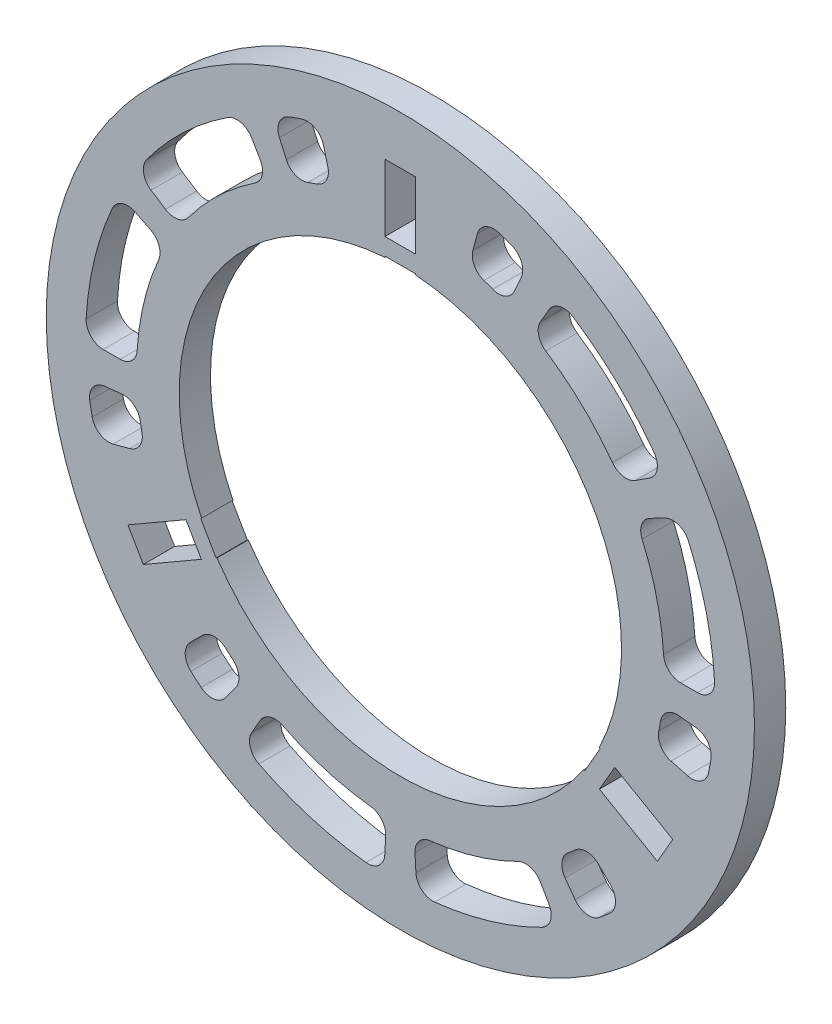
SolidWorks part; units mm, degrees
ref_plane "Front Plane" through (0, 0, 0) normal (0, 0, 1) x (1, 0, 0)
ref_plane "Top Plane" through (0, 0, 0) normal (0, 1, 0) x (1, 0, 0)
ref_plane "Right Plane" through (0, 0, 0) normal (1, 0, 0) x (0, 0, -1)
sketch "Sketch1" plane through (0, 0, 0) normal (0, 0, 1) x (1, 0, 0)
  line L0 (0, 0) -> (0, 50.8) construction
  line L1 (47.9712, -31.0114) -> (50.8422, -26.0386)
  line L2 (2.871, 57.05) -> (-2.871, 57.05)
  line L3 (2.871, 57.05) -> (2.871, 44.55)
  line L4 (2.871, 44.55) -> (-2.871, 44.55)
  line L5 (-2.871, 57.05) -> (-2.871, 44.55)
  line L6 (2.871, 57.05) -> (-2.871, 44.55) construction
  line L7 (2.871, 44.55) -> (-2.871, 57.05) construction
  line L8 (47.9712, -31.0114) -> (37.1459, -24.7614)
  line L9 (37.1459, -24.7614) -> (40.0169, -19.7886)
  line L10 (50.8422, -26.0386) -> (40.0169, -19.7886)
  line L11 (47.9712, -31.0114) -> (40.0169, -19.7886) construction
  line L12 (37.1459, -24.7614) -> (50.8422, -26.0386) construction
  line L13 (-50.8422, -26.0386) -> (-47.9712, -31.0114)
  line L14 (-50.8422, -26.0386) -> (-40.0169, -19.7886)
  line L15 (-40.0169, -19.7886) -> (-37.1459, -24.7614)
  line L16 (-47.9712, -31.0114) -> (-37.1459, -24.7614)
  line L17 (-50.8422, -26.0386) -> (-37.1459, -24.7614) construction
  line L18 (-40.0169, -19.7886) -> (-47.9712, -31.0114) construction
  line L19 (-2.871, 41.375) -> (2.871, 41.375)
  line L20 (-2.871, 41.175) -> (-2.871, 41.375)
  line L21 (2.871, 41.175) -> (2.871, 41.375)
  line L22 (34.2231, -23.0739) -> (34.3963, -23.1739)
  line L23 (37.2673, -18.2011) -> (34.3963, -23.1739)
  line L24 (37.0941, -18.1012) -> (37.2673, -18.2011)
  line L25 (-37.0941, -18.1012) -> (-37.2673, -18.2011)
  line L26 (-34.3963, -23.1739) -> (-37.2673, -18.2011)
  line L27 (0, 0) -> (32.5438, 56.3674) construction
  line L28 (-34.2231, -23.0739) -> (-34.3963, -23.1739)
  arc A0 (-2.871, 41.175) -> (-37.0941, -18.1012) centre (0, 0) ccw
  circle A1 centre (0, 0) radius 65.0875
  circle A2 centre (0, 0) radius 50.8 construction
  arc A3 (37.0941, -18.1012) -> (2.871, 41.175) centre (0, 0) ccw
  arc A4 (-34.2231, -23.0739) -> (34.2231, -23.0739) centre (0, 0) ccw
  point P21 (0, 0)
  point P32 (0, 0)
  point P34 (0, 0)
  dimension "D1" = 82.55
  dimension "D2" = 130.175
  dimension "D8" = 3.175
  dimension "D10" = 101.6
  dimension "D3" = 50.8
  dimension "D4" = 12.5
  dimension "D5" = 5.742
  dimension "D7" = 30
  dimension "D6" = 3
  dimension "D9" = 3
extrude "Boss-Extrude1" add sketch "Sketch1" along normal blind 5.842
sketch "Sketch3" plane through (0, 0, 5.842) normal (0, 0, 1) x (1, 0, 0)
  line L0 (0, 0) -> (0, 65.0875) construction
  line L1 (0, 0) -> (-56.3674, 32.5437) construction
  line L2 (-24.6063, 42.6193) -> (-29.3688, 50.8682)
  line L3 (-49.2125, 0) -> (-58.7375, 0)
  line L4 (-41.2731, 26.803) -> (-49.2614, 31.9907)
  line L5 (-43.8487, 22.342) -> (-52.3355, 26.6663)
  line L6 (43.8487, 22.342) -> (52.3355, 26.6663)
  line L7 (41.2731, 26.803) -> (49.2614, 31.9907)
  line L8 (24.6063, 42.6193) -> (29.3688, 50.8682)
  line L9 (49.2125, 0) -> (58.7375, 0)
  line L10 (-2.5756, -49.1451) -> (-3.0741, -58.657)
  line L11 (2.5756, -49.1451) -> (3.0741, -58.657)
  line L12 (24.6062, -42.6193) -> (29.3687, -50.8682)
  line L13 (-24.6063, -42.6193) -> (-29.3688, -50.8682)
  line L14 (-20.0165, 44.9579) -> (-23.8907, 53.6594)
  line L15 (-15.2024, 56.7361) -> (-12.7371, 47.5356)
  line L16 (-56.7361, -15.2024) -> (-47.5356, -12.7371)
  line L17 (-48.9429, -5.1441) -> (-58.4157, -6.1397)
  line L18 (48.9429, -5.1441) -> (58.4157, -6.1397)
  line L19 (56.7361, -15.2024) -> (47.5356, -12.7371)
  line L20 (15.2024, 56.7361) -> (12.7371, 47.5356)
  line L21 (20.0165, 44.9579) -> (23.8907, 53.6594)
  line L22 (-28.9264, -39.8137) -> (-34.525, -47.5196)
  line L23 (-41.5337, -41.5337) -> (-34.7985, -34.7985)
  line L24 (41.5337, -41.5337) -> (34.7985, -34.7985)
  line L25 (28.9264, -39.8137) -> (34.525, -47.5196)
  circle A0 centre (0, 0) radius 65.0875 construction
  arc A1 (-29.3688, 50.8682) -> (-49.2614, 31.9907) centre (0, 0) ccw
  arc A2 (-24.6063, 42.6193) -> (-41.2731, 26.803) centre (0, 0) ccw
  arc A3 (-43.8487, 22.342) -> (-49.2125, 0) centre (0, 0) ccw
  circle A4 centre (0, 0) radius 49.2125 construction
  circle A5 centre (0, 0) radius 58.7375 construction
  arc A6 (-52.3355, 26.6663) -> (-58.7375, 0) centre (0, 0) ccw
  arc A7 (58.7375, 0) -> (52.3355, 26.6663) centre (0, 0) ccw
  arc A8 (49.2614, 31.9907) -> (29.3688, 50.8682) centre (0, 0) ccw
  arc A9 (41.2731, 26.803) -> (24.6063, 42.6193) centre (0, 0) ccw
  arc A10 (49.2125, 0) -> (43.8487, 22.342) centre (0, 0) ccw
  arc A11 (-29.3688, -50.8682) -> (-3.0741, -58.657) centre (0, 0) ccw
  arc A12 (3.0741, -58.657) -> (29.3687, -50.8682) centre (0, 0) ccw
  arc A13 (2.5756, -49.1451) -> (24.6062, -42.6193) centre (0, 0) ccw
  arc A14 (-24.6063, -42.6193) -> (-2.5756, -49.1451) centre (0, 0) ccw
  arc A15 (-24.6063, 42.6193) -> (-41.2731, 26.803) centre (0, 0) ccw
  arc A16 (-29.3688, 50.8682) -> (-49.2614, 31.9907) centre (0, 0) ccw
  arc A17 (-43.8487, 22.342) -> (-49.2125, 0) centre (0, 0) ccw
  arc A18 (-52.3355, 26.6663) -> (-58.7375, 0) centre (0, 0) ccw
  arc A19 (-24.6063, -42.6193) -> (-2.5756, -49.1451) centre (0, 0) ccw
  arc A20 (-29.3688, -50.8682) -> (-3.0741, -58.657) centre (0, 0) ccw
  arc A21 (2.5756, -49.1451) -> (24.6062, -42.6193) centre (0, 0) ccw
  arc A22 (3.0741, -58.657) -> (29.3687, -50.8682) centre (0, 0) ccw
  arc A23 (58.7375, 0) -> (52.3355, 26.6663) centre (0, 0) ccw
  arc A24 (49.2125, 0) -> (43.8487, 22.342) centre (0, 0) ccw
  arc A25 (41.2731, 26.803) -> (24.6063, 42.6193) centre (0, 0) ccw
  arc A26 (49.2614, 31.9907) -> (29.3688, 50.8682) centre (0, 0) ccw
  arc A27 (-12.7371, 47.5356) -> (-20.0165, 44.9579) centre (0, 0) ccw
  arc A28 (-15.2024, 56.7361) -> (-23.8907, 53.6594) centre (0, 0) ccw
  arc A29 (-56.7361, -15.2024) -> (-58.4157, -6.1397) centre (0, 0) cw
  arc A30 (-47.5356, -12.7371) -> (-48.9429, -5.1441) centre (0, 0) cw
  arc A31 (56.7361, -15.2024) -> (58.4157, -6.1397) centre (0, 0) ccw
  arc A32 (47.5356, -12.7371) -> (48.9429, -5.1441) centre (0, 0) ccw
  arc A33 (15.2024, 56.7361) -> (23.8907, 53.6594) centre (0, 0) cw
  arc A34 (12.7371, 47.5356) -> (20.0165, 44.9579) centre (0, 0) cw
  arc A35 (-41.5337, -41.5337) -> (-34.525, -47.5196) centre (0, 0) ccw
  arc A36 (-34.7985, -34.7985) -> (-28.9264, -39.8137) centre (0, 0) ccw
  arc A37 (41.5337, -41.5337) -> (34.525, -47.5196) centre (0, 0) cw
  arc A38 (34.7985, -34.7985) -> (28.9264, -39.8137) centre (0, 0) cw
  point P8 (56.171, 17.1732)
  point P13 (49.2125, 0)
  point P38 (0, 0)
  point P63 (0, 0)
  dimension "D2" = 117.475
  dimension "D1" = 60
  dimension "D4" = 30
  dimension "D5" = 3
  dimension "D7" = 36
  dimension "D8" = 45
  dimension "D3" = 9.525
  dimension "D6" = 3
  dimension "D9" = 3
extrude "Cut-Extrude2" cut sketch "Sketch3" against normal through all contours A2 L2 A1 L4 | L5 A6 L3 A3 | L16 A30 L17 A29 | L15 A28 L14 A27 | L20 A34 L21 A33 | A9 L7 A8 L8 | A10 L9 A7 L6 | A32 L19 A31 L18 | L24 A38 L25 A37 | A13 L11 A12 L12 | A14 L13 A11 L10 | A36 L23 A35 L22 region at (-36.9066, 38.8915, 5.842) region at (-52.1343, 12.5163, 5.842) region at (52.1343, 12.5163, 5.842) region at (36.9066, 38.8915, 5.842) region at (-15.2277, -51.4078, 5.842) region at (15.2277, -51.4078, 5.842) region at (-18.0454, 50.9587, 5.842) region at (-53.1542, -9.8516, 5.842) region at (53.1542, -9.8516, 5.842) region at (18.0454, 50.9587, 5.842) region at (-35.1088, -41.1071, 5.842) region at (35.1088, -41.1071, 5.842)
fillet "Fillet1" radius 3.175 48 edges at (-52.3355, 26.6663, 2.921) (-58.4157, -6.1397, 2.921) (-43.8487, 22.342, 2.921) (-48.9429, -5.1441, 2.921) (-58.7375, 0, 2.921) (-56.7361, -15.2024, 2.921) (-47.5356, -12.7371, 2.921) (-49.2125, 0, 2.921) (-41.2731, 26.803, 2.921) (-49.2614, 31.9907, 2.921) (-20.0165, 44.9579, 2.921) (-12.7371, 47.5356, 2.921) (-15.2024, 56.7361, 2.921) (-23.8907, 53.6594, 2.921) (-29.3688, 50.8682, 2.921) (-24.6063, 42.6193, 2.921) (41.5337, -41.5337, 2.921) (34.525, -47.5196, 2.921) (34.7985, -34.7985, 2.921) (28.9264, -39.8137, 2.921) (3.0741, -58.657, 2.921) (2.5756, -49.1451, 2.921) (24.6062, -42.6193, 2.921) (29.3687, -50.8682, 2.921) (-3.0741, -58.657, 2.921) (-2.5756, -49.1451, 2.921) (-29.3688, -50.8682, 2.921) (-24.6063, -42.6193, 2.921) (-28.9264, -39.8137, 2.921) (-41.5337, -41.5337, 2.921) (-34.7985, -34.7985, 2.921) (-34.525, -47.5196, 2.921) (48.9429, -5.1441, 2.921) (58.4157, -6.1397, 2.921) (56.7361, -15.2024, 2.921) (47.5356, -12.7371, 2.921) (58.7375, 0, 2.921) (49.2125, 0, 2.921) (52.3355, 26.6663, 2.921) (43.8487, 22.342, 2.921) (49.2614, 31.9907, 2.921) (41.2731, 26.803, 2.921) (29.3688, 50.8682, 2.921) (23.8907, 53.6594, 2.921) (15.2024, 56.7361, 2.921) (24.6063, 42.6193, 2.921) (12.7371, 47.5356, 2.921) (20.0165, 44.9579, 2.921)
sketch "Sketch4" plane through (0, 0, 5.842) normal (0, 0, 1) x (1, 0, 0)
  circle A0 centre (0, 0) radius 65.0875
  circle A1 centre (0, 0) radius 66.0875
  point P3 (0, 0)
  dimension "D1" = 1
extrude "Boss-Extrude2" add sketch "Sketch4" against normal up to surface (5.842 mm away) up to face at (-15.0326, -50.7493, 0)
